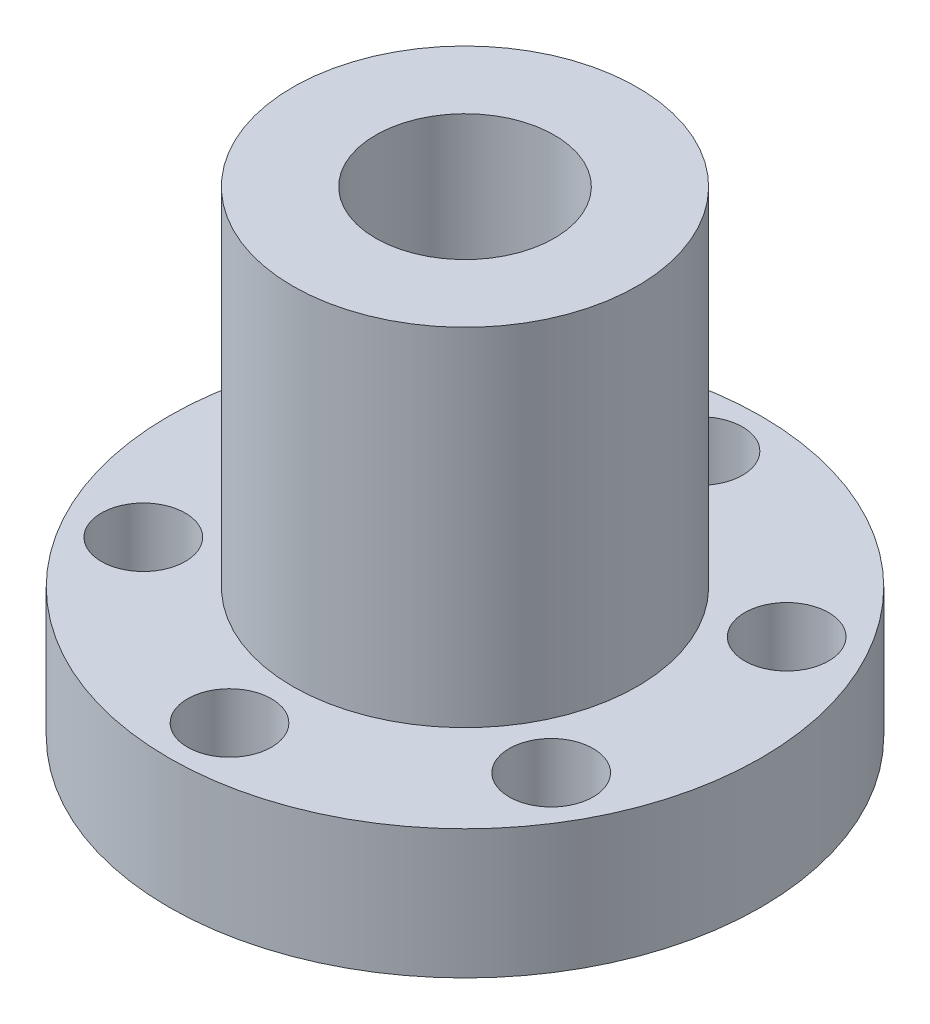
SolidWorks part; units mm, degrees
ref_plane "Front" through (0, 0, 0) normal (0, 0, 1) x (1, 0, 0)
ref_plane "Top" through (0, 0, 0) normal (0, 1, 0) x (1, 0, 0)
ref_plane "Right" through (0, 0, 0) normal (1, 0, 0) x (0, 0, -1)
sketch "Sketch1" plane through (0, 0, 0) normal (0, 1, 0) x (1, 0, 0)
  circle A0 centre (0, 0) radius 27.5
  circle A1 centre (0, 0) radius 16
  dimension "D1" = 32
  dimension "D2" = 55
extrude "Boss-Extrude1" add sketch "Sketch1" along normal blind 12
extrude "Boss-Extrude2" add sketch "Sketch1<2>" along normal blind 44.2 contours A1
sketch "Sketch1<2>" plane through (0, 0, 0) normal (0, 1, 0) x (1, 0, 0) same geometry as "Sketch1"
sketch "Sketch3" plane through (0, 0, 0) normal (0, 1, 0) x (1, 0, 0)
  line L0 (0, -27.5) -> (0, -16.2399) construction
  circle A0 centre (0, 0) radius 8.3
  circle A1 centre (0, 0) radius 27.5 construction
  circle A2 centre (0, -21.87) radius 3.9
  circle A3 centre (-18.9399, -10.935) radius 3.9
  circle A4 centre (-18.9399, 10.935) radius 3.9
  circle A5 centre (0, 21.87) radius 3.9
  circle A6 centre (18.9399, 10.935) radius 3.9
  circle A7 centre (18.9399, -10.935) radius 3.9
  point P22 (0, 0)
  dimension "D1" = 6
  dimension "D2" = 16.6
  dimension "D3" = 7.8
extrude "Cut-Extrude1" cut sketch "Sketch3" along normal through all
